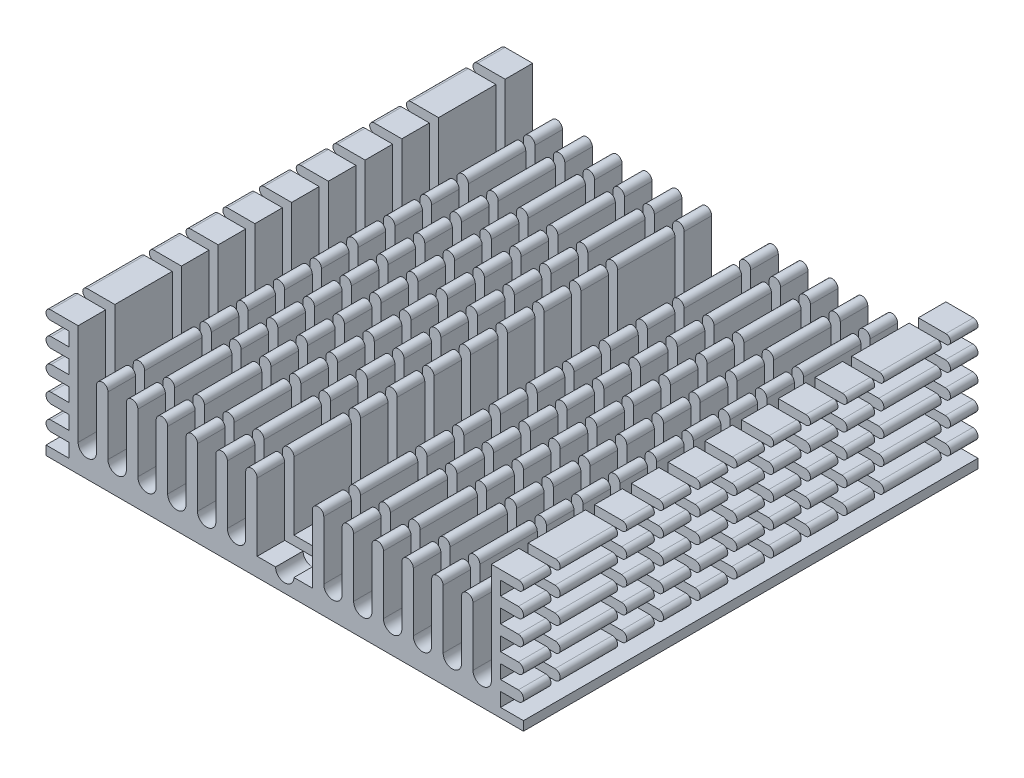
SolidWorks part; units mm, degrees
ref_plane "Plan de face" through (0, 0, 0) normal (0, 0, 1) x (1, 0, 0)
ref_plane "Plan de dessus" through (0, 0, 0) normal (0, 1, 0) x (1, 0, 0)
ref_plane "Plan de droite" through (0, 0, 0) normal (1, 0, 0) x (0, 0, -1)
sketch "Esquisse1" plane through (0, 0, 0) normal (0, 0, 1) x (1, 0, 0)
  line L0 (-26, 14) -> (-22.5, 14)
  line L1 (-26, 0) -> (26, 0)
  line L2 (-26, 0) -> (-26, 14)
  line L3 (-26, 14) -> (26, 14) construction
  line L4 (26, 0) -> (26, 14)
  line L5 (-22.5, 14) -> (-22.5, 10)
  line L6 (-22.5, 10) -> (22.5, 10)
  line L7 (22.5, 10) -> (22.5, 14)
  line L8 (22.5, 14) -> (26, 14)
  dimension "D1" = 52
  dimension "D2" = 14
  dimension "D3" = 10
  dimension "D4" = 3.5
extrude "Boss.-Extru.1" add sketch "Esquisse1" along normal mid plane 49.5
sketch "Esquisse2" plane through (0, 0, 24.75) normal (0, 0, 1) x (1, 0, 0)
  line L0 (-22.5, 10) -> (-22.5, 3)
  line L1 (-20.5, 10) -> (-20.5, 3)
  line L2 (22.5, 10) -> (-22.5, 10) construction
  line L3 (-21.5, 2) -> (-21.5, 0) construction
  line L4 (-26, 0) -> (26, 0) construction
  line L5 (-22.5, 10) -> (-20.5, 10)
  line L6 (-19.25, 10) -> (-17.25, 10)
  line L7 (-19.25, 10) -> (-19.25, 3)
  line L8 (-17.25, 10) -> (-17.25, 3)
  line L9 (-16, 10) -> (-14, 10)
  line L10 (-16, 10) -> (-16, 3)
  line L11 (-14, 10) -> (-14, 3)
  line L12 (-12.75, 10) -> (-10.75, 10)
  line L13 (-12.75, 10) -> (-12.75, 3)
  line L14 (-10.75, 10) -> (-10.75, 3)
  line L15 (-9.5, 10) -> (-7.5, 10)
  line L16 (-9.5, 10) -> (-9.5, 3)
  line L17 (-7.5, 10) -> (-7.5, 3)
  line L18 (-6.25, 10) -> (-4.25, 10)
  line L19 (-6.25, 10) -> (-6.25, 3)
  line L20 (-4.25, 10) -> (-4.25, 3)
  line L21 (0, 0) -> (0, 10) construction
  line L22 (21.5, 2) -> (21.5, 0) construction
  line L23 (4.25, 10) -> (4.25, 3)
  line L24 (6.25, 10) -> (6.25, 3)
  line L25 (6.25, 10) -> (4.25, 10)
  line L26 (7.5, 10) -> (7.5, 3)
  line L27 (9.5, 10) -> (9.5, 3)
  line L28 (9.5, 10) -> (7.5, 10)
  line L29 (10.75, 10) -> (10.75, 3)
  line L30 (12.75, 10) -> (12.75, 3)
  line L31 (12.75, 10) -> (10.75, 10)
  line L32 (14, 10) -> (14, 3)
  line L33 (16, 10) -> (16, 3)
  line L34 (16, 10) -> (14, 10)
  line L35 (17.25, 10) -> (17.25, 3)
  line L36 (19.25, 10) -> (19.25, 3)
  line L37 (19.25, 10) -> (17.25, 10)
  line L38 (22.5, 10) -> (20.5, 10)
  line L39 (20.5, 10) -> (20.5, 3)
  line L40 (22.5, 10) -> (22.5, 3)
  line L41 (1, 2) -> (3, 2)
  line L42 (-3, 10) -> (3, 10)
  line L43 (-3, 10) -> (-3, 2)
  line L44 (-3, 2) -> (-1, 2)
  line L45 (3, 10) -> (3, 2)
  line L46 (-26, 14) -> (-26, 0) construction
  line L47 (-26, 13) -> (-23.5, 13)
  line L48 (-26, 13) -> (-26, 11.5)
  line L49 (-26, 11.5) -> (-23.5, 11.5)
  line L50 (-23.5, 13) -> (-23.5, 11.5)
  line L51 (-22.5, 14) -> (-26, 14) construction
  line L52 (-22.5, 10) -> (-22.5, 14) construction
  line L53 (-26, 10.375) -> (-23.5, 10.375)
  line L54 (-23.5, 10.375) -> (-23.5, 8.875)
  line L55 (-26, 10.375) -> (-26, 8.875)
  line L56 (-26, 8.875) -> (-23.5, 8.875)
  line L57 (-26, 7.75) -> (-23.5, 7.75)
  line L58 (-23.5, 7.75) -> (-23.5, 6.25)
  line L59 (-26, 7.75) -> (-26, 6.25)
  line L60 (-26, 6.25) -> (-23.5, 6.25)
  line L61 (-26, 5.125) -> (-23.5, 5.125)
  line L62 (-23.5, 5.125) -> (-23.5, 3.625)
  line L63 (-26, 5.125) -> (-26, 3.625)
  line L64 (-26, 3.625) -> (-23.5, 3.625)
  line L65 (-26, 2.5) -> (-23.5, 2.5)
  line L66 (-23.5, 2.5) -> (-23.5, 1)
  line L67 (-26, 2.5) -> (-26, 1)
  line L68 (-26, 1) -> (-23.5, 1)
  line L69 (26, 1) -> (23.5, 1)
  line L70 (26, 2.5) -> (26, 1)
  line L71 (23.5, 2.5) -> (23.5, 1)
  line L72 (26, 2.5) -> (23.5, 2.5)
  line L73 (26, 3.625) -> (23.5, 3.625)
  line L74 (26, 5.125) -> (26, 3.625)
  line L75 (23.5, 5.125) -> (23.5, 3.625)
  line L76 (26, 5.125) -> (23.5, 5.125)
  line L77 (26, 6.25) -> (23.5, 6.25)
  line L78 (26, 7.75) -> (26, 6.25)
  line L79 (23.5, 7.75) -> (23.5, 6.25)
  line L80 (26, 7.75) -> (23.5, 7.75)
  line L81 (26, 8.875) -> (23.5, 8.875)
  line L82 (26, 10.375) -> (26, 8.875)
  line L83 (23.5, 10.375) -> (23.5, 8.875)
  line L84 (26, 10.375) -> (23.5, 10.375)
  line L85 (23.5, 13) -> (23.5, 11.5)
  line L86 (26, 11.5) -> (23.5, 11.5)
  line L87 (26, 13) -> (26, 11.5)
  line L88 (26, 13) -> (23.5, 13)
  arc A0 (-22.5, 3) -> (-20.5, 3) centre (-21.5, 3) ccw
  arc A1 (-19.25, 3) -> (-17.25, 3) centre (-18.25, 3) ccw
  arc A2 (-16, 3) -> (-14, 3) centre (-15, 3) ccw
  arc A3 (-12.75, 3) -> (-10.75, 3) centre (-11.75, 3) ccw
  arc A4 (-9.5, 3) -> (-7.5, 3) centre (-8.5, 3) ccw
  arc A5 (-6.25, 3) -> (-4.25, 3) centre (-5.25, 3) ccw
  arc A6 (6.25, 3) -> (4.25, 3) centre (5.25, 3) cw
  arc A7 (9.5, 3) -> (7.5, 3) centre (8.5, 3) cw
  arc A8 (12.75, 3) -> (10.75, 3) centre (11.75, 3) cw
  arc A9 (16, 3) -> (14, 3) centre (15, 3) cw
  arc A10 (19.25, 3) -> (17.25, 3) centre (18.25, 3) cw
  arc A11 (22.5, 3) -> (20.5, 3) centre (21.5, 3) cw
  arc A12 (-1, 2) -> (1, 2) centre (0, 2) ccw
  dimension "D7" = 1
  dimension "D1" = 2
  dimension "D2" = 2
  dimension "D4" = 1.25
  dimension "D5" = 6
  dimension "D6" = 2
  dimension "D8" = 1.5
  dimension "D9" = 1
  dimension "D10" = 1
  dimension "D12" = 1
  dimension "D3" = 6
  dimension "D11" = 5
extrude "Enlèv. mat.-Extru.1" cut sketch "Esquisse2" against normal blind 49.5
sketch "Esquisse4" plane through (0, 0, 0) normal (1, 0, 0) x (0, 0, -1)
  line L0 (0, 14) -> (0, 0) construction
  line L1 (-24.75, 14) -> (24.75, 14) construction
  line L2 (24.75, 1) -> (-24.75, 1) construction
  line L3 (-2.5, 14) -> (-1.5, 14)
  line L4 (-2.5, 14) -> (-2.5, 1)
  line L5 (-2.5, 1) -> (-1.5, 1)
  line L6 (-1.5, 14) -> (-1.5, 1)
  line L7 (-6.5, 14) -> (-6.5, 1)
  line L8 (-6.5, 14) -> (-5.5, 14)
  line L9 (-5.5, 14) -> (-5.5, 1)
  line L10 (-6.5, 1) -> (-5.5, 1)
  line L11 (-10.5, 14) -> (-10.5, 1)
  line L12 (-10.5, 14) -> (-9.5, 14)
  line L13 (-9.5, 14) -> (-9.5, 1)
  line L14 (-10.5, 1) -> (-9.5, 1)
  line L15 (-14.5, 14) -> (-14.5, 1)
  line L16 (-14.5, 14) -> (-13.5, 14)
  line L17 (-13.5, 14) -> (-13.5, 1)
  line L18 (-14.5, 1) -> (-13.5, 1)
  line L19 (24.75, 1) -> (-24.75, 1) construction
  line L20 (-21.75, 14) -> (-20.75, 14)
  line L21 (-21.75, 14) -> (-21.75, 1)
  line L22 (-21.75, 1) -> (-20.75, 1)
  line L23 (-20.75, 14) -> (-20.75, 1)
  line L24 (-24.75, 13) -> (-24.75, 11.5) construction
  line L25 (20.75, 14) -> (20.75, 1)
  line L26 (21.75, 1) -> (20.75, 1)
  line L27 (21.75, 14) -> (21.75, 1)
  line L28 (21.75, 14) -> (20.75, 14)
  line L29 (14.5, 1) -> (13.5, 1)
  line L30 (13.5, 14) -> (13.5, 1)
  line L31 (14.5, 14) -> (13.5, 14)
  line L32 (14.5, 14) -> (14.5, 1)
  line L33 (10.5, 1) -> (9.5, 1)
  line L34 (9.5, 14) -> (9.5, 1)
  line L35 (10.5, 14) -> (9.5, 14)
  line L36 (10.5, 14) -> (10.5, 1)
  line L37 (6.5, 1) -> (5.5, 1)
  line L38 (5.5, 14) -> (5.5, 1)
  line L39 (6.5, 14) -> (5.5, 14)
  line L40 (6.5, 14) -> (6.5, 1)
  line L41 (1.5, 14) -> (1.5, 1)
  line L42 (2.5, 1) -> (1.5, 1)
  line L43 (2.5, 14) -> (2.5, 1)
  line L44 (2.5, 14) -> (1.5, 14)
  point P32 (-24.75, 12.25)
  dimension "D1" = 3
  dimension "D2" = 1
  dimension "D4" = 3
  dimension "D5" = 3
  dimension "D3" = 4
extrude "Enlèv. mat.-Extru.2" cut sketch "Esquisse4" against normal through all both and the other way through all
sketch "Esquisse5" plane through (0, 0, 0) normal (0, 1, 0) x (1, 0, 0)
  line L0 (0, 0) -> (0, 24.75) construction
  line L1 (1, 24.75) -> (-1, 24.75) construction
  line L2 (1, 24.75) -> (3, 24.75) construction
  circle A0 centre (0, 13.75) radius 2.25
  circle A1 centre (0, -5.25) radius 2.25
  point P9 (2, 24.75)
  dimension "D1" = 4.5
  dimension "D2" = 11
  dimension "D3" = 19
extrude "Enlèv. mat.-Extru.4" cut sketch "Esquisse5" along normal through all
sketch "Esquisse6" plane through (0, 0, 24.75) normal (0, 0, 1) x (1, 0, 0)
  line L0 (-20.5, 3) -> (-20.5, 10) construction
  line L1 (-19.25, 10) -> (-19.25, 3) construction
  line L2 (-19.25, 10) -> (-20.5, 10) construction
  line L3 (-20.5, 9.375) -> (-20.5, 10.625)
  line L4 (-20.5, 10.625) -> (-19.25, 10.625)
  line L5 (-19.25, 10.625) -> (-19.25, 9.375)
  line L6 (0, 0) -> (0, 1) construction
  line L7 (-26, 0) -> (26, 0) construction
  line L8 (-17.25, 10.625) -> (-16, 10.625)
  line L9 (-17.25, 9.375) -> (-17.25, 10.625)
  line L10 (-16, 10.625) -> (-16, 9.375)
  line L11 (-14, 10.625) -> (-12.75, 10.625)
  line L12 (-14, 9.375) -> (-14, 10.625)
  line L13 (-12.75, 10.625) -> (-12.75, 9.375)
  line L14 (-10.75, 10.625) -> (-9.5, 10.625)
  line L15 (-10.75, 9.375) -> (-10.75, 10.625)
  line L16 (-9.5, 10.625) -> (-9.5, 9.375)
  line L17 (-7.5, 10.625) -> (-6.25, 10.625)
  line L18 (-7.5, 9.375) -> (-7.5, 10.625)
  line L19 (-6.25, 10.625) -> (-6.25, 9.375)
  line L20 (-4.25, 10.625) -> (-3, 10.625)
  line L21 (-4.25, 9.375) -> (-4.25, 10.625)
  line L22 (-3, 10.625) -> (-3, 9.375)
  line L23 (-3, 10) -> (-3, 2) construction
  line L24 (3, 10.625) -> (3, 9.375)
  line L25 (4.25, 9.375) -> (4.25, 10.625)
  line L26 (4.25, 10.625) -> (3, 10.625)
  line L27 (6.25, 10.625) -> (6.25, 9.375)
  line L28 (7.5, 9.375) -> (7.5, 10.625)
  line L29 (7.5, 10.625) -> (6.25, 10.625)
  line L30 (9.5, 10.625) -> (9.5, 9.375)
  line L31 (10.75, 9.375) -> (10.75, 10.625)
  line L32 (10.75, 10.625) -> (9.5, 10.625)
  line L33 (12.75, 10.625) -> (12.75, 9.375)
  line L34 (14, 9.375) -> (14, 10.625)
  line L35 (14, 10.625) -> (12.75, 10.625)
  line L36 (16, 10.625) -> (16, 9.375)
  line L37 (17.25, 9.375) -> (17.25, 10.625)
  line L38 (17.25, 10.625) -> (16, 10.625)
  line L39 (19.25, 10.625) -> (19.25, 9.375)
  line L40 (20.5, 10.625) -> (19.25, 10.625)
  line L41 (20.5, 9.375) -> (20.5, 10.625)
  line L42 (-22.5, 14) -> (-26, 14) construction
  line L43 (-23.5, 13) -> (-26, 13) construction
  line L44 (-26, 14) -> (-26, 13) construction
  line L45 (-25.5, 14) -> (-26.5, 14)
  line L46 (-26.5, 14) -> (-26.5, 13)
  line L47 (-26.5, 13) -> (-25.5, 13)
  line L48 (-26, 11.5) -> (-23.5, 11.5) construction
  line L49 (-23.5, 10.375) -> (-26, 10.375) construction
  line L50 (-26, 11.5) -> (-26, 10.375) construction
  line L51 (-25.4375, 11.5) -> (-26.5625, 11.5)
  line L52 (-26.5625, 11.5) -> (-26.5625, 10.375)
  line L53 (-26.5625, 10.375) -> (-25.4375, 10.375)
  line L54 (-25.4375, 8.875) -> (-26.5625, 8.875)
  line L55 (-26.5625, 8.875) -> (-26.5625, 7.75)
  line L56 (-26.5625, 7.75) -> (-25.4375, 7.75)
  line L57 (-25.4375, 6.25) -> (-26.5625, 6.25)
  line L58 (-26.5625, 6.25) -> (-26.5625, 5.125)
  line L59 (-26.5625, 5.125) -> (-25.4375, 5.125)
  line L60 (-25.4375, 3.625) -> (-26.5625, 3.625)
  line L61 (-26.5625, 3.625) -> (-26.5625, 2.5)
  line L62 (-26.5625, 2.5) -> (-25.4375, 2.5)
  line L63 (-23.5, 2.5) -> (-26, 2.5) construction
  line L64 (26.5625, 2.5) -> (25.4375, 2.5)
  line L65 (26.5625, 3.625) -> (26.5625, 2.5)
  line L66 (25.4375, 3.625) -> (26.5625, 3.625)
  line L67 (26.5625, 5.125) -> (25.4375, 5.125)
  line L68 (26.5625, 6.25) -> (26.5625, 5.125)
  line L69 (25.4375, 6.25) -> (26.5625, 6.25)
  line L70 (26.5625, 7.75) -> (25.4375, 7.75)
  line L71 (26.5625, 8.875) -> (26.5625, 7.75)
  line L72 (25.4375, 8.875) -> (26.5625, 8.875)
  line L73 (26.5625, 10.375) -> (25.4375, 10.375)
  line L74 (26.5625, 11.5) -> (26.5625, 10.375)
  line L75 (25.4375, 11.5) -> (26.5625, 11.5)
  line L76 (26.5, 13) -> (25.5, 13)
  line L77 (26.5, 14) -> (26.5, 13)
  line L78 (25.5, 14) -> (26.5, 14)
  arc A0 (-20.5, 9.375) -> (-19.25, 9.375) centre (-19.875, 9.375) cw
  arc A1 (-1, 2) -> (1, 2) centre (0, 2) ccw construction
  arc A2 (-17.25, 9.375) -> (-16, 9.375) centre (-16.625, 9.375) cw
  arc A3 (-14, 9.375) -> (-12.75, 9.375) centre (-13.375, 9.375) cw
  arc A4 (-10.75, 9.375) -> (-9.5, 9.375) centre (-10.125, 9.375) cw
  arc A5 (-7.5, 9.375) -> (-6.25, 9.375) centre (-6.875, 9.375) cw
  arc A6 (-4.25, 9.375) -> (-3, 9.375) centre (-3.625, 9.375) cw
  arc A7 (4.25, 9.375) -> (3, 9.375) centre (3.625, 9.375) ccw
  arc A8 (7.5, 9.375) -> (6.25, 9.375) centre (6.875, 9.375) ccw
  arc A9 (10.75, 9.375) -> (9.5, 9.375) centre (10.125, 9.375) ccw
  arc A10 (14, 9.375) -> (12.75, 9.375) centre (13.375, 9.375) ccw
  arc A11 (17.25, 9.375) -> (16, 9.375) centre (16.625, 9.375) ccw
  arc A12 (20.5, 9.375) -> (19.25, 9.375) centre (19.875, 9.375) ccw
  arc A13 (-25.5, 14) -> (-25.5, 13) centre (-25.5, 13.5) ccw
  arc A14 (-25.4375, 11.5) -> (-25.4375, 10.375) centre (-25.4375, 10.9375) ccw
  arc A15 (-25.4375, 8.875) -> (-25.4375, 7.75) centre (-25.4375, 8.3125) ccw
  arc A16 (-25.4375, 6.25) -> (-25.4375, 5.125) centre (-25.4375, 5.6875) ccw
  arc A17 (-25.4375, 3.625) -> (-25.4375, 2.5) centre (-25.4375, 3.0625) ccw
  arc A18 (25.4375, 3.625) -> (25.4375, 2.5) centre (25.4375, 3.0625) cw
  arc A19 (25.4375, 6.25) -> (25.4375, 5.125) centre (25.4375, 5.6875) cw
  arc A20 (25.4375, 8.875) -> (25.4375, 7.75) centre (25.4375, 8.3125) cw
  arc A21 (25.4375, 11.5) -> (25.4375, 10.375) centre (25.4375, 10.9375) cw
  arc A22 (25.5, 14) -> (25.5, 13) centre (25.5, 13.5) cw
  point P99 (-25.4415, 2.5)
  dimension "D2" = 4
  dimension "D1" = 6
extrude "Enlèv. mat.-Extru.5" cut sketch "Esquisse6" against normal through all
